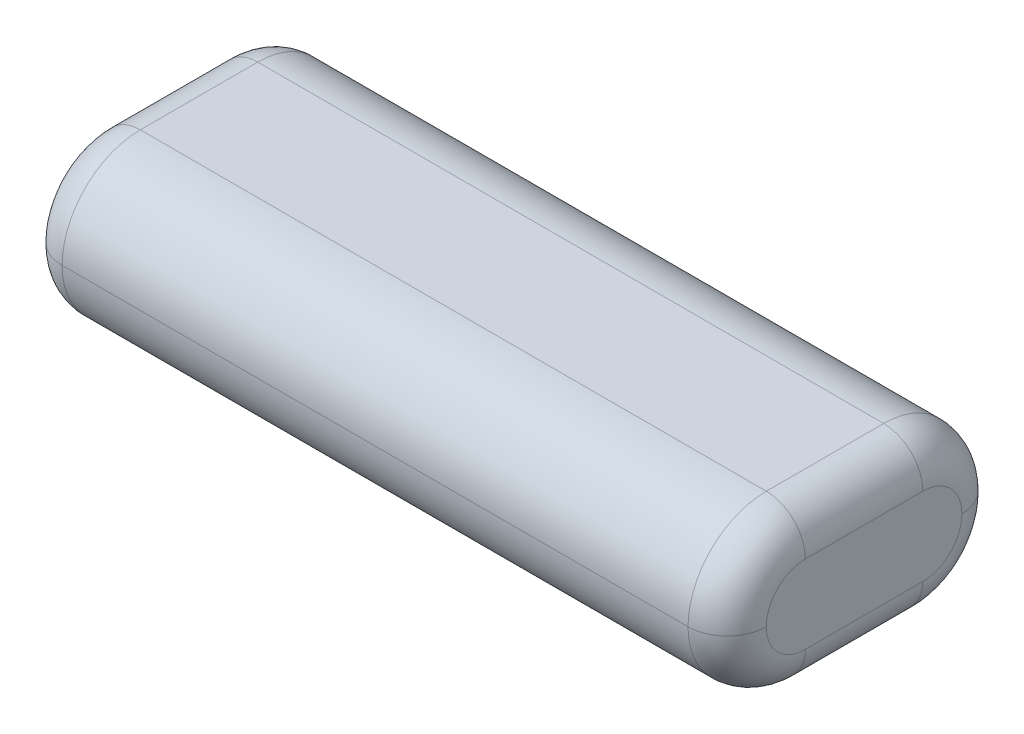
SolidWorks part; units mm, degrees
ref_plane "Front Plane" through (0, 0, 0) normal (0, 0, 1) x (1, 0, 0)
ref_plane "Top Plane" through (0, 0, 0) normal (0, 1, 0) x (1, 0, 0)
ref_plane "Right Plane" through (0, 0, 0) normal (1, 0, 0) x (0, 0, -1)
sketch "Sketch1" plane through (0, 0, 0) normal (0, 1, 0) x (1, 0, 0)
  line L1 (0, 0) -> (90, 0)
  line L2 (0, 0) -> (0, 35)
  line L3 (0, 35) -> (90, 35)
  line L4 (90, 0) -> (90, 35)
  dimension "D1" = 35
  dimension "D2" = 90
extrude "Boss-Extrude1" add sketch "Sketch1" along normal blind 20
fillet "Fillet1" radius 10 4 edges at (45, 20, -35) (45, 0, -35) (45, 0, 0) (45, 20, 0)
fillet "Fillet2" radius 5 12 edges at (0, 17.0711, -32.0711) (0, 2.9289, -32.0711) (0, 0, -17.5) (0, 2.9289, -2.9289) (0, 17.0711, -2.9289) (90, 17.0711, -2.9289) (90, 2.9289, -2.9289) (90, 0, -17.5) (90, 2.9289, -32.0711) (90, 17.0711, -32.0711) (0, 20, -17.5) (90, 20, -17.5)
